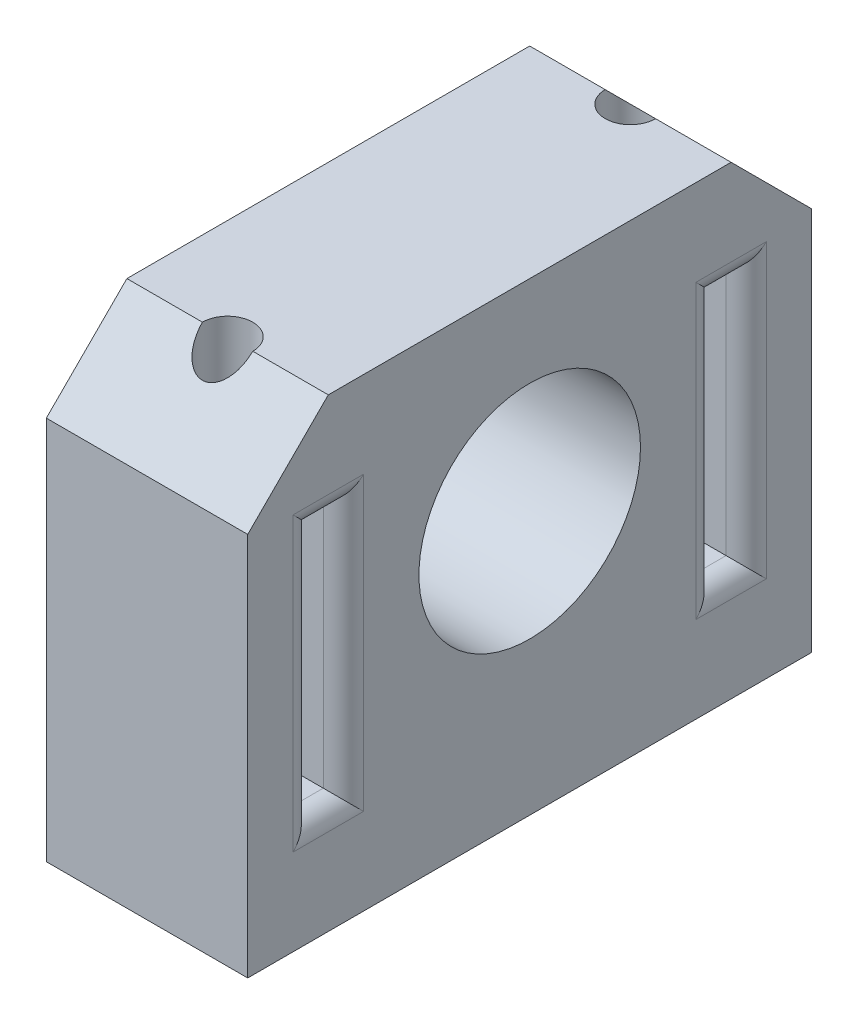
SolidWorks part; units mm, degrees
ref_plane "정면" through (0, 0, 0) normal (0, 0, 1) x (1, 0, 0)
ref_plane "윗면" through (0, 0, 0) normal (0, 1, 0) x (1, 0, 0)
ref_plane "우측면" through (0, 0, 0) normal (1, 0, 0) x (0, 0, -1)
sketch "스케치2" plane through (0, 0, 0) normal (1, 0, 0) x (0, 0, -1)
  line L1 (-28, -26.15) -> (28, -26.15)
  line L2 (-28, -26.15) -> (-28, 20)
  line L3 (-28, 20) -> (28, 20)
  line L4 (28, -26.15) -> (28, 20)
  circle A0 centre (0, 0) radius 11
  dimension "D1" = 22
  dimension "D2" = 26.15
  dimension "D3" = 56
  dimension "D4" = 20
extrude "보스-돌출1" add sketch "스케치2" along normal blind 20
sketch "스케치3" plane through (0, 20, 0) normal (0, 1, 0) x (1, 0, 0)
  line L0 (0, 0) -> (20, 0) construction
  line L1 (0, 28) -> (0, -28) construction
  line L2 (20, 28) -> (20, -28) construction
  line L3 (10, 0) -> (10, 28) construction
  line L4 (20, 28) -> (0, 28) construction
  circle A0 centre (10, 20) radius 2.5
  circle A1 centre (10, -20) radius 2.5
  dimension "D1" = 5
  dimension "D2" = 8
extrude "컷-돌출1" cut sketch "스케치3" against normal through all
sketch "스케치4" plane through (20, 0, 0) normal (1, 0, 0) x (0, 0, -1)
  line L0 (0, 20) -> (0, -26.15) construction
  line L1 (28, 20) -> (-28, 20) construction
  line L2 (-28, -26.15) -> (28, -26.15) construction
  line L3 (-28, 20) -> (-28, -26.15) construction
  line L4 (-21.5, 9.425) -> (-18.5, 9.425)
  line L5 (-21.5, 9.425) -> (-21.5, -15.575)
  line L6 (-21.5, -15.575) -> (-18.5, -15.575)
  line L7 (-18.5, 9.425) -> (-18.5, -15.575)
  line L8 (-21.5, -3.075) -> (-18.5, -3.075) construction
  line L9 (21.5, -15.575) -> (18.5, -15.575)
  line L10 (18.5, 9.425) -> (18.5, -15.575)
  line L11 (21.5, 9.425) -> (18.5, 9.425)
  line L12 (21.5, 9.425) -> (21.5, -15.575)
  dimension "D1" = 3
  dimension "D2" = 6.5
  dimension "D3" = 25
extrude "컷-돌출2" cut sketch "스케치4" against normal through all
chamfer "모따기1" distance 8 angle 45 2 edges at (10, 20, -28) (10, 20, 28)
fillet "필렛1" radius 1 16 edges at (8, -3.075, 21.5) (7.5, 9.425, 20) (12.5, 9.425, 20) (12.5, -15.575, 20) (7.5, -15.575, 20) (12, -3.075, 21.5) (8, -3.075, 18.5) (12, -3.075, 18.5) (7.5, 9.425, -20) (8, -3.075, -21.5) (8, -3.075, -18.5) (7.5, -15.575, -20) (12.5, -15.575, -20) (12.5, 9.425, -20) (12, -3.075, -21.5) (12, -3.075, -18.5)
fillet "필렛2" radius 2 16 edges at (0, -3.075, -21.5) (0, -15.575, -20) (0, -3.075, -18.5) (0, 9.425, -20) (0, 9.425, 20) (0, -3.075, 18.5) (0, -3.075, 21.5) (0, -15.575, 20) (20, 9.425, 20) (20, -3.075, 21.5) (20, -3.075, 18.5) (20, -15.575, 20) (20, 9.425, -20) (20, -3.075, -18.5) (20, -3.075, -21.5) (20, -15.575, -20)
